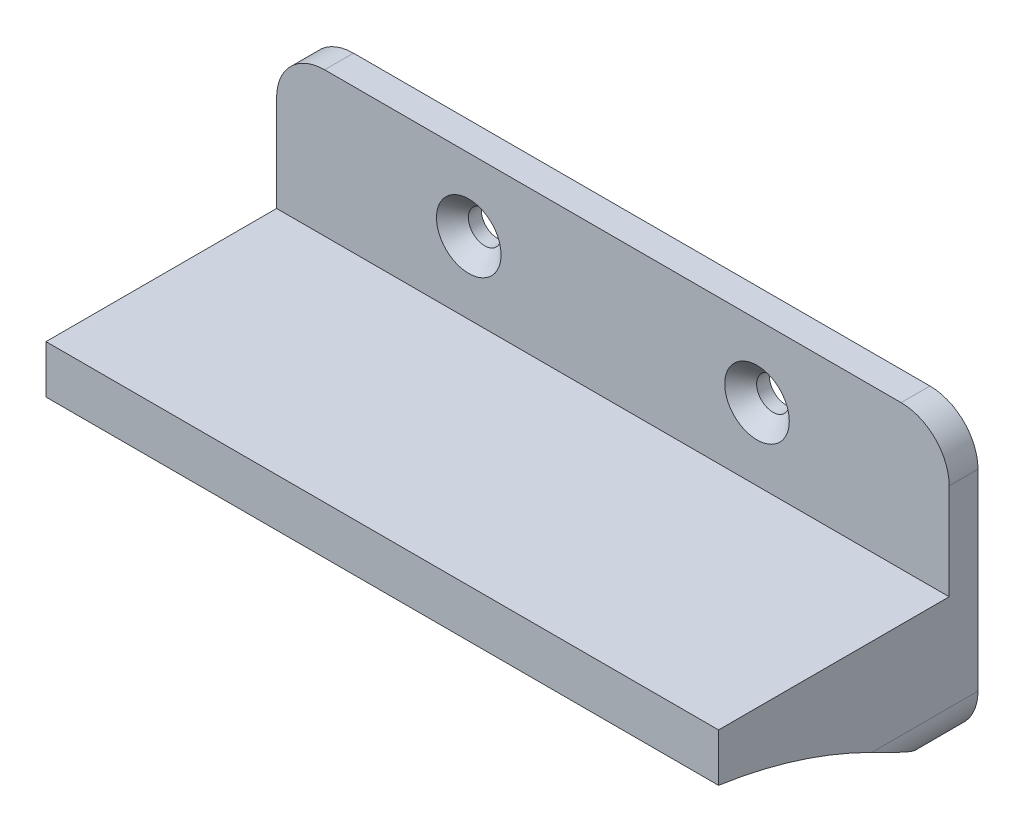
SolidWorks part; units mm, degrees
ref_plane "Alzado" through (0, 0, 0) normal (0, 0, 1) x (1, 0, 0)
ref_plane "Planta" through (0, 0, 0) normal (0, 1, 0) x (1, 0, 0)
ref_plane "Vista lateral" through (0, 0, 0) normal (1, 0, 0) x (0, 0, -1)
sketch "Croquis1" plane through (0, 0, 0) normal (0, 0, 1) x (1, 0, 0)
  line L1 (-29.9237, 15.4962) -> (40.0763, 15.4962)
  line L2 (-29.9237, 15.4962) -> (-29.9237, -14.5038)
  line L3 (-29.9237, -14.5038) -> (40.0763, -14.5038)
  line L4 (40.0763, 15.4962) -> (40.0763, -14.5038)
  dimension "D1" = 70
  dimension "D2" = 30
extrude "Saliente-Extruir1" add sketch "Croquis1" along normal blind 3
sketch "Croquis3" plane through (0, 0, 3) normal (0, 0, 1) x (1, 0, 0)
  line L0 (-29.9237, 15.4962) -> (-29.9237, -14.5038) construction
  line L1 (-29.9237, 0.4962) -> (40.0763, 0.4962)
  line L2 (-29.9237, 0.4962) -> (-29.9237, -4.5038)
  line L3 (-25.9237, -4.5038) -> (-7.9237, -4.5038)
  line L4 (40.0763, 0.4962) -> (40.0763, -4.5038)
  line L5 (40.0763, -14.5038) -> (40.0763, 15.4962) construction
  line L6 (-29.9237, -14.5038) -> (40.0763, -14.5038) construction
  line L7 (-7.9237, -4.5038) -> (-7.9237, -14.5038)
  line L9 (-29.9237, -4.5038) -> (-29.9237, -14.5038)
  line L10 (-29.9237, -14.5038) -> (-25.9237, -14.5038)
  line L11 (-25.9237, -4.5038) -> (-25.9237, -14.5038)
  line L13 (-3.9237, -4.5038) -> (-3.9237, -14.5038)
  line L14 (-7.9237, -14.5038) -> (-3.9237, -14.5038)
  line L15 (14.0763, -4.5038) -> (14.0763, -14.5038)
  line L17 (18.0763, -4.5038) -> (18.0763, -14.5038)
  line L18 (14.0763, -14.5038) -> (18.0763, -14.5038)
  line L19 (36.0763, -4.5038) -> (36.0763, -14.5038)
  line L21 (40.0763, -4.5038) -> (40.0763, -14.5038)
  line L22 (36.0763, -14.5038) -> (40.0763, -14.5038)
  line L23 (-3.9237, -4.5038) -> (14.0763, -4.5038)
  line L24 (18.0763, -4.5038) -> (36.0763, -4.5038)
  dimension "D1" = 5
  dimension "D2" = 10
  dimension "D3" = 4
  dimension "D4" = 4
extrude "Saliente-Extruir2" add sketch "Croquis3" along normal blind 24
sketch "Croquis4" plane through (-29.9237, 0, 0) normal (-1, 0, 0) x (0, 0, 1)
  line L0 (27, -14.5038) -> (27, -4.5038)
  line L1 (27, 0.4962) -> (27, -14.5038) construction
  line L2 (3, 0.4962) -> (3, -14.5038) construction
  line L3 (27, -14.5038) -> (0, -14.5038) construction
  line L4 (27, -14.5038) -> (3, -14.5038)
  arc A0 (3, -14.5038) -> (27, -4.5038) centre (34.43, -56.1358) cw
  dimension "D1" = 10
extrude "Cortar-Extruir1" cut sketch "Croquis4" against normal up to vertex (70 mm away) up to point (40.0763, 0.4962, 27)
sketch "Croquis5" plane through (0, 0, 3) normal (0, 0, 1) x (1, 0, 0)
  line L0 (-29.9237, 15.4962) -> (-29.9237, 0.4962) construction
  line L1 (5.0763, 15.4962) -> (5.0763, 0.4962) construction
  line L2 (40.0763, 15.4962) -> (-29.9237, 15.4962) construction
  line L3 (40.0763, 0.4962) -> (-29.9237, 0.4962) construction
  circle A0 centre (-9.9237, 7.9962) radius 1.5
  circle A1 centre (20.0763, 7.9962) radius 1.5
  dimension "D1" = 20
  dimension "D2" = 3
extrude "Cortar-Extruir2" cut sketch "Croquis5" against normal up to vertex (3 mm away) up to point (-29.9237, 15.4962, 0)
hole_wizard "Refrentado para tornillo tapón con cabeza plana de clavija de M31" positions "Croquis6" profile "Croquis7" countersink size "M3" standard "Ansi Metric" end condition through all
sketch "Croquis6" plane through (0, 0, 3) normal (0, 0, 1) x (1, 0, 0)
  point P0 (-9.9237, 7.9962)
  point P3 (20.0763, 7.9962)
sketch "Croquis7" plane through (-9.9237, 7.9962, 3) normal (1, 0, 0) x (0, -1, 0)
  line L0 (0, 0) -> (0, 3)
  line L1 (0, 3) -> (1.7, 3)
  line L2 (1.7, 3) -> (1.7, 1.66)
  line L3 (1.7, 1.66) -> (3.36, 0)
  line L5 (3.36, 0) -> (0, 0)
  line L6 (-1.7, 1.66) -> (-3.36, 0) construction
  line L11 (0, -6.35) -> (0, 107.95) construction
  dimension "Diámetro de taladro hasta el siguiente" = 3.4
  dimension "Profundidad de taladro hasta el siguiente" = 3
  dimension "Diámetro de avellanado cercano" = 6.72
  dimension "Ángulo de avellanado cercano" = 90
fillet "Redondeo1" radius 5 4 edges at (40.0763, -14.5038, 1.5) (-29.9237, -14.5038, 1.5) (40.0763, 15.4962, 1.5) (-29.9237, 15.4962, 1.5)
